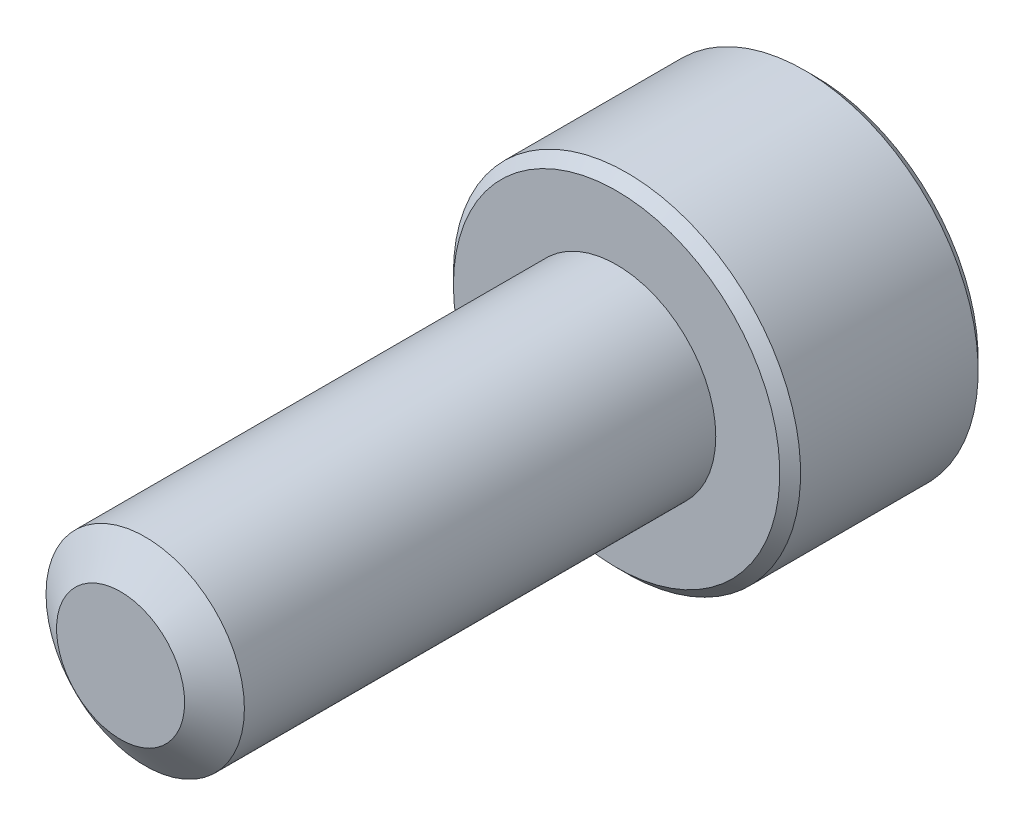
SolidWorks part; units mm, degrees
material "Alloy Steel"
ref_plane "Front Plane" through (0, 0, 0) normal (0, 0, 1) x (1, 0, 0)
ref_plane "Top Plane" through (0, 0, 0) normal (0, 1, 0) x (1, 0, 0)
ref_plane "Right Plane" through (0, 0, 0) normal (1, 0, 0) x (0, 0, -1)
sketch "Sketch1" plane through (0, 0, 0) normal (0, 0, 1) x (1, 0, 0)
  circle A0 centre (0, 0) radius 2
  dimension "OD" = 4
extrude "Extrude1" add sketch "Sketch1" against normal blind 10
sketch "Sketch2" plane through (0, 0, 0) normal (0, 0, 1) x (1, 0, 0)
  circle A0 centre (0, 0) radius 2 construction
  circle A1 centre (0, 0) radius 2
curve "Helix/Spiral1" pitch 0.7 height 10.7 turns 15.2857 parameters "pitch"=0.7
sketch "Sketch3" plane through (0, 0, 0) normal (1, 0, 0) x (0, 0, -1)
  line L0 (-0.6125, 2) -> (-0.35, 1.5453)
  line L1 (-0.35, 1.5453) -> (-0.2625, 1.5453)
  line L2 (-0.2625, 1.5453) -> (0, 2)
  line L3 (-0.6125, 2) -> (0, 2)
  line L4 (-0.3063, 2) -> (-0.3063, 1.5453) construction
  line L5 (-0.4813, 1.7727) -> (-0.1313, 1.7727) construction
  line L6 (0, 2) -> (0, -2) construction
  line L7 (0, -2) -> (10, -2) construction
  point P11 (3.15, -2)
  dimension "D1" = 0.0875
  dimension "D2" = 0.35
  dimension "D3" = 60
  dimension "D4" = 3.15
sweep "Cut-Sweep1" [suppressed] cut profiles "Sketch3" path "Helix/Spiral1"
sketch "Sketch4" plane through (0, 0, 0) normal (1, 0, 0) x (0, 0, -1)
  line L0 (0.4962, 2) -> (0, 1.2913)
  line L1 (0, 1.2913) -> (0, 2)
  line L2 (0.4962, 2) -> (0, 2)
  line L3 (-0.6125, 2) -> (0, 2) construction
  line L4 (0, 0) -> (7.0209, 0) construction
  dimension "D1" = 55
  dimension "D2" = 0.254
revolve "Cut-Revolve1" cut sketch "Sketch4" angle 360 about L4
sketch "Sketch5" [suppressed] plane through (0, 0, 0) normal (1, 0, 0) x (0, 0, -1)
  line L0 (10, 0.3311) -> (10, 1.814) construction
  line L1 (10, 2) -> (0.1203, 2)
  line L2 (10, 2) -> (10, 0)
  line L3 (10, 0) -> (0.0001, 0)
  line L4 (0.0001, 1.6698) -> (0.0001, 0)
  line L5 (0.1203, 2) -> (0.0001, 1.6698)
  line L6 (0, 0) -> (9.9695, 0) construction
  point P3 (0.0001, 2)
  point P10 (0.0001, 2)
  dimension "D1" = 0.3302
  dimension "Thread min" = 0.0001
  dimension "D3" = 20
revolve "partially thread" [suppressed] add sketch "Sketch5" angle 360 about L6
sketch "Sketch6" plane through (0, 0, -10) normal (0, 0, -1) x (-1, 0, 0)
  circle A0 centre (0, 0) radius 3.5
  dimension "head dia" = 7
extrude "Extrude2" add sketch "Sketch6" along normal blind 4
sketch "Sketch7" plane through (0, 0, -14) normal (0, 0, -1) x (-1, 0, 0)
  line L1 (0, 1.7321) -> (-1.5, 0.866)
  line L2 (-1.5, 0.866) -> (-1.5, -0.866)
  line L3 (-1.5, -0.866) -> (0, -1.7321)
  line L4 (0, -1.7321) -> (1.5, -0.866)
  line L5 (1.5, -0.866) -> (1.5, 0.866)
  line L6 (1.5, 0.866) -> (0, 1.7321)
  circle A0 centre (0, 0) radius 1.5 construction
  dimension "hex dia" = 3
extrude "Cut-Extrude1" cut sketch "Sketch7" against normal blind 2.25
sketch "Sketch8" plane through (0, 0, -14) normal (0, 0, -1) x (-1, 0, 0)
  circle A0 centre (0, 0) radius 1.7321
extrude "Cut-Extrude2" cut sketch "Sketch8" against normal through all draft 45
chamfer "Chamfer1" distance 0.21 angle 45 2 edges at (-3.5, 0, -14) (-3.5, 0, -10)
sketch "Sketch9" plane through (0, 0, 0) normal (1, 0, 0) x (0, 0, -1)
  line L0 (0, 2) -> (0, -2) construction
  line L1 (3.85, 2) -> (3.85, -2) construction
  dimension "D1" = 3.85
sketch "Sketch10" plane through (0, 0, 0) normal (1, 0, 0) x (0, 0, -1)
  line L0 (10, 2) -> (10, 0)
  line L1 (10, 2) -> (9.825, 2)
  line L2 (9.825, 2) -> (8.9966, 0)
  line L3 (10, 0) -> (8.9966, 0)
  line L4 (10, 3.29) -> (10, -3.29) construction
  dimension "D1" = 22.5
  dimension "D2" = 0.175
revolve "Revolve1" add sketch "Sketch10" angle 360 about L3
equation "\"D3@Helix/Spiral1\" = \"screw length@Extrude1\"+\"pitch@Helix/Spiral1\""
equation "\"D1@Sketch3\" = \"pitch@Helix/Spiral1\"*.125"
equation "\"D2@Sketch3\" = \"pitch@Helix/Spiral1\"*.5"
equation "\"D1@Cut-Extrude1\" = \"hex dia@Sketch7\"*.75"
equation "\"D1@Chamfer1\" = \"head dia@Sketch6\"*.03"
equation "\"D1@Sketch9\" = \"pitch@Helix/Spiral1\"*5.5"
equation "\"D2@Sketch10\" = \"pitch@Helix/Spiral1\"*.25"
equation "\"D4@Sketch3\" = \"pitch@Helix/Spiral1\"*4.50"
